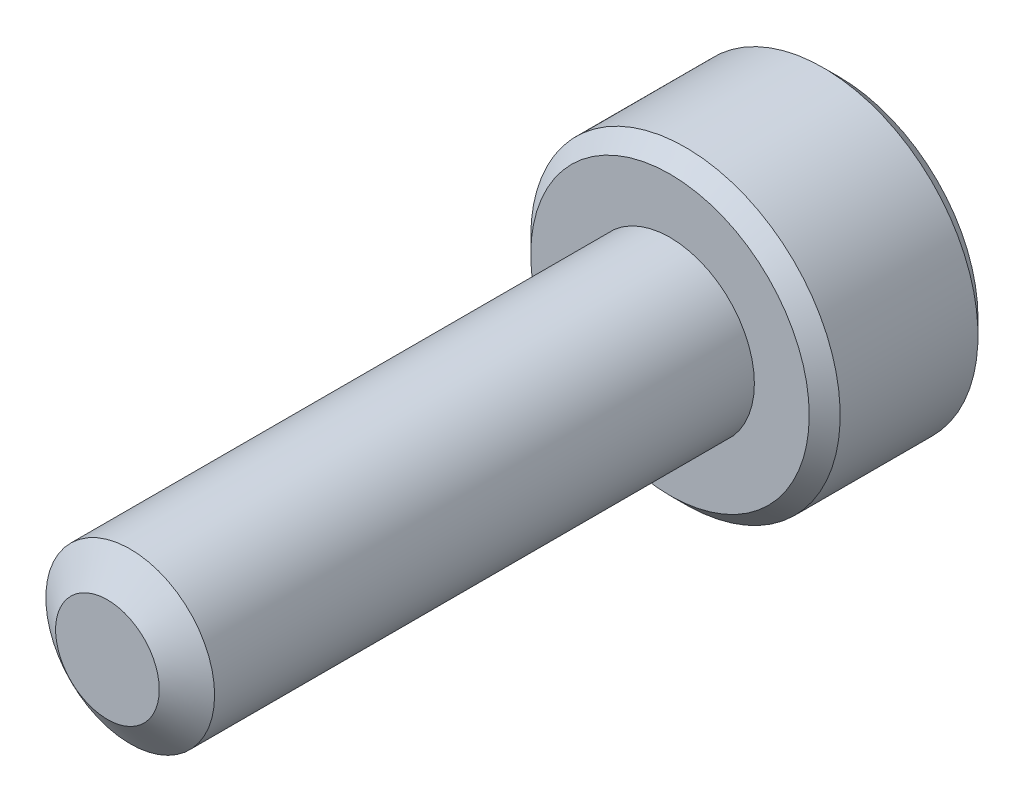
SolidWorks part; units mm, degrees
other "DetailItem1"
ref_plane "Front Plane" through (0, 0, 0) normal (0, 0, 1) x (1, 0, 0)
ref_plane "Top Plane" through (0, 0, 0) normal (0, 1, 0) x (1, 0, 0)
ref_plane "Right Plane" through (0, 0, 0) normal (1, 0, 0) x (0, 0, -1)
sketch "Sketch1" plane through (0, 0, 0) normal (0, 0, 1) x (1, 0, 0)
  circle A0 centre (0, 0) radius 1.5
  dimension "OD" = 3
extrude "Extrude1" add sketch "Sketch1" against normal blind 10
sketch "Sketch2" plane through (0, 0, 0) normal (0, 0, 1) x (1, 0, 0)
  circle A0 centre (0, 0) radius 1.5 construction
  circle A1 centre (0, 0) radius 1.5
curve "Helix/Spiral1" pitch 0.5 height 10.5 turns 21 parameters "pitch"=0.5
sketch "Sketch3" plane through (0, 0, 0) normal (1, 0, 0) x (0, 0, -1)
  line L0 (-0.4375, 1.5) -> (-0.25, 1.1752)
  line L1 (-0.25, 1.1752) -> (-0.1875, 1.1752)
  line L2 (-0.1875, 1.1752) -> (0, 1.5)
  line L3 (-0.4375, 1.5) -> (0, 1.5)
  line L4 (-0.2187, 1.5) -> (-0.2188, 1.1752) construction
  line L5 (-0.3438, 1.3376) -> (-0.0938, 1.3376) construction
  line L6 (0, 1.5) -> (0, -1.5) construction
  dimension "D1" = 0.0625
  dimension "D2" = 0.25
  dimension "D3" = 60
sweep "Cut-Sweep1" [suppressed] cut profiles "Sketch3" path "Helix/Spiral1"
sketch "Sketch4" plane through (0, 0, 0) normal (1, 0, 0) x (0, 0, -1)
  line L0 (0.4053, 1.5) -> (0, 0.9212)
  line L1 (0, 0.9212) -> (0, 1.5)
  line L2 (0.4053, 1.5) -> (0, 1.5)
  line L3 (-0.4375, 1.5) -> (0, 1.5) construction
  line L4 (0, 0) -> (7.0209, 0) construction
  dimension "D1" = 55
  dimension "D2" = 0.254
revolve "Cut-Revolve1" cut sketch "Sketch4" angle 360 about L4
sketch "Sketch6" plane through (0, 0, -10) normal (0, 0, -1) x (-1, 0, 0)
  circle A0 centre (0, 0) radius 2.75
  dimension "head dia" = 5.5
extrude "Extrude2" add sketch "Sketch6" along normal blind 3
sketch "Sketch7" plane through (0, 0, -13) normal (0, 0, -1) x (-1, 0, 0)
  line L1 (0, 1.4434) -> (-1.25, 0.7217)
  line L2 (-1.25, 0.7217) -> (-1.25, -0.7217)
  line L3 (-1.25, -0.7217) -> (0, -1.4434)
  line L4 (0, -1.4434) -> (1.25, -0.7217)
  line L5 (1.25, -0.7217) -> (1.25, 0.7217)
  line L6 (1.25, 0.7217) -> (0, 1.4434)
  circle A0 centre (0, 0) radius 1.25 construction
  dimension "hex dia" = 2.5
extrude "Cut-Extrude1" cut sketch "Sketch7" against normal blind 1.875
sketch "Sketch8" plane through (0, 0, -13) normal (0, 0, -1) x (-1, 0, 0)
  circle A0 centre (0, 0) radius 1.4434
extrude "Cut-Extrude2" cut sketch "Sketch8" against normal through all draft 45
chamfer "Chamfer1" distance 0.275 angle 45 2 edges at (-2.75, 0, -13) (-2.75, 0, -10)
sketch "Sketch10" plane through (0, 0, -10) normal (0, 0, 1) x (1, 0, 0)
  circle A1 centre (0, 0) radius 1.5
  circle A2 centre (0, 0) radius 1.5
  dimension "D1" = 0
ref_plane "Plane1" through (0, 0, 0) normal (0, 0, 1) x (1, 0, 0)
extrude "partial thread" [suppressed] add sketch "Sketch10" along normal up to surface (4 mm away) separate body
chamfer "Chamfer2" [suppressed] distance 0.06 angle 45
combine bodies "Combine1" [suppressed] operation type add bodies to combine 107 108
sketch "Sketch9" plane through (0, 0, 0) normal (1, 0, 0) x (0, 0, -1)
  line L0 (0, 1.5) -> (0, -1.5) construction
  line L1 (1.25, 1.5) -> (1.25, -1.5) construction
  dimension "D1" = 1.25
equation "\"D3@Helix/Spiral1\" = \"screw length@Extrude1\"+\"pitch@Helix/Spiral1\""
equation "\"D1@Sketch3\" = \"pitch@Helix/Spiral1\"*.125"
equation "\"D2@Sketch3\" = \"pitch@Helix/Spiral1\"*.5"
equation "\"D1@Cut-Extrude1\" = \"hex dia@Sketch7\"*.75"
equation "\"D1@Chamfer1\" = \"head dia@Sketch6\"*.05"
equation "\"D1@Sketch9\" = \"pitch@Helix/Spiral1\"*2.5"
equation "\"D1@Chamfer2\"=\"OD@Sketch1\"*.02"
